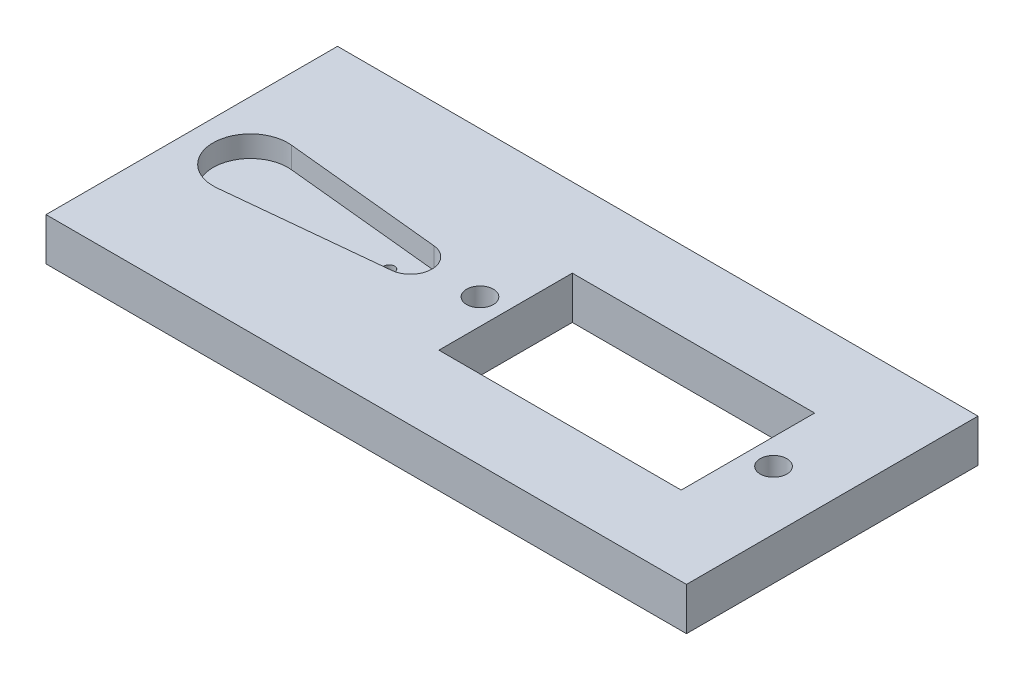
SolidWorks part; units mm, degrees
ref_plane "前视基准面" through (0, 0, 0) normal (0, 0, 1) x (1, 0, 0)
ref_plane "上视基准面" through (0, 0, 0) normal (0, 1, 0) x (1, 0, 0)
ref_plane "右视基准面" through (0, 0, 0) normal (1, 0, 0) x (0, 0, -1)
other "Configuration Table"
sketch "草图1" plane through (0, 0, 0) normal (0, 1, 0) x (1, 0, 0)
  line L0 (-24.15, 3.4825) -> (-9.3, 1.99)
  line L1 (-30, 13.6546) -> (30, 13.6546)
  line L2 (-30, 13.6546) -> (-30, -13.6546)
  line L3 (-30, -13.6546) -> (30, -13.6546)
  line L4 (30, 13.6546) -> (30, -13.6546)
  line L5 (-30, 13.6546) -> (30, -13.6546) construction
  line L6 (-30, -13.6546) -> (30, 13.6546) construction
  line L7 (-0.6, 6.25) -> (22.1, 6.25)
  line L8 (-0.6, 6.25) -> (-0.6, -6.25)
  line L9 (-0.6, -6.25) -> (22.1, -6.25)
  line L10 (22.1, 6.25) -> (22.1, -6.25)
  line L11 (-0.6, 6.25) -> (22.1, -6.25) construction
  line L12 (-0.6, -6.25) -> (22.1, 6.25) construction
  line L13 (-24.15, -3.4825) -> (-9.3, -1.99)
  line L14 (10.75, -8.5449) -> (10.75, 8.614) construction
  circle A0 centre (-24.5, 0) radius 3.5
  circle A1 centre (-11.5, 0) radius 0.5
  circle A2 centre (-9.5, 0) radius 2
  circle A3 centre (-3, 0) radius 1.25
  circle A4 centre (24.5, 0) radius 1.25
  point P0 (0, 0)
  point P12 (10.75, 0)
  point P21 (-30, 0)
  point P31 (30, 0)
  dimension "D1" = 7
  dimension "D2" = 4
  dimension "D3" = 1
  dimension "D5" = 13
  dimension "D6" = 5.5
  dimension "D8" = 12.5
  dimension "D9" = 17.1589
  dimension "D10" = 27.5
  dimension "D11" = 5.5
  dimension "D12" = 2.5
  dimension "D13" = 27.3092
  dimension "D4" = 15
  dimension "D7" = 22.7
  dimension "D14" = 60
extrude "凸台-拉伸2" add sketch "草图1" along normal blind 4 contours L4 L1 L2 L3 A4 A3 A2 L13 A0 L0 L7 L10 L9 L8 region at (-0.9183, 0, 0)
extrude "凸台-拉伸3" add sketch "草图1<4>" along normal blind 2 contours A0 | A2 L0 A0 L13 A1 | A2 A1 region at (-16.7322, 0, 0) region at (-24.5, 0, 0) region at (-9.4458, 0, 0)
sketch "草图1<4>" plane through (0, 0, 0) normal (0, 1, 0) x (1, 0, 0) same geometry as "草图1"
